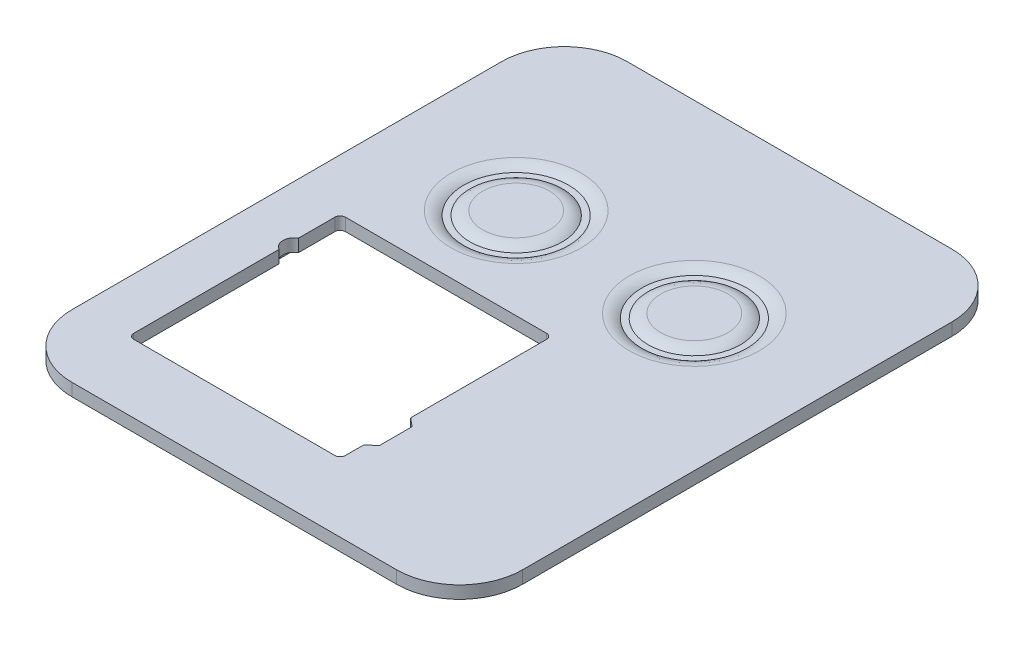
SolidWorks part; units mm, degrees
ref_plane "Front Plane" through (0, 0, 0) normal (0, 0, 1) x (1, 0, 0)
ref_plane "Top Plane" through (0, 0, 0) normal (0, 1, 0) x (1, 0, 0)
ref_plane "Right Plane" through (0, 0, 0) normal (1, 0, 0) x (0, 0, -1)
sketch "Sketch1" plane through (0, 0, 0) normal (0, 1, 0) x (1, 0, 0)
  line L1 (-7.75, -13.25) -> (7.75, -13.25)
  line L2 (-10.75, -10.25) -> (-10.75, 10.25)
  line L3 (-7.75, 13.25) -> (7.75, 13.25)
  line L4 (10.75, -10.25) -> (10.75, 10.25)
  line L5 (-10.75, -13.25) -> (10.75, 13.25) construction
  line L6 (-10.75, 13.25) -> (10.75, -13.25) construction
  arc A0 (-7.75, -13.25) -> (-10.75, -10.25) centre (-7.75, -10.25) cw
  arc A1 (7.75, -13.25) -> (10.75, -10.25) centre (7.75, -10.25) ccw
  arc A2 (7.75, 13.25) -> (10.75, 10.25) centre (7.75, 10.25) cw
  arc A3 (-10.75, 10.25) -> (-7.75, 13.25) centre (-7.75, 10.25) cw
  point P0 (0, 0)
  dimension "D3" = 3
  dimension "D1" = 21.5
  dimension "D2" = 26.5
extrude "Boss-Extrude1" add sketch "Sketch1" along normal blind 0.6
sketch "Sketch2" plane through (0, 0.6, 0) normal (0, 1, 0) x (1, 0, 0)
  line L1 (1.55, -0.15) -> (-8.05, -0.15) construction
  line L2 (1.55, -0.15) -> (1.55, -9.75) construction
  line L3 (1.55, -9.75) -> (-8.05, -9.75) construction
  line L4 (-8.05, -0.15) -> (-8.05, -9.75) construction
  line L6 (-10.75, 10.25) -> (-10.75, -10.25) construction
  line L7 (-7.75, -13.25) -> (7.75, -13.25) construction
  line L9 (1.55, -10) -> (-8.05, -10)
  line L10 (1.8, -9.75) -> (1.8, -0.15)
  line L11 (1.55, 0.1) -> (-8.05, 0.1)
  line L12 (-8.3, -9.75) -> (-8.3, -0.15)
  arc A0 (-8.05, -10) -> (-8.3, -9.75) centre (-8.05, -9.75) cw
  arc A1 (1.55, -10) -> (1.8, -9.75) centre (1.55, -9.75) ccw
  arc A2 (1.8, -0.15) -> (1.55, 0.1) centre (1.55, -0.15) ccw
  arc A3 (-8.05, 0.1) -> (-8.3, -0.15) centre (-8.05, -0.15) ccw
  dimension "D9" = 0.25
  dimension "D1" = 2.7
  dimension "D2" = 3.5
  dimension "D3" = 9.6
  dimension "D4" = 9.6
  dimension "D5" = 0.25
  dimension "D6" = 0.25
  dimension "D7" = 0.25
  dimension "D8" = 0.25
extrude "Cut-Extrude1" cut sketch "Sketch2" against normal blind 2
sketch "Sketch3" plane through (0, 0.6, 0) normal (0, 1, 0) x (1, 0, 0)
  line L2 (2.2, -6.9693) -> (2.2, -8.5311)
  line L3 (2.2, -8.5311) -> (1.8, -8.8672)
  line L5 (2.2, -6.9693) -> (1.8, -6.6332)
  line L6 (1.8, -9.75) -> (1.8, -0.15) construction
  line L7 (-10.75, 10.25) -> (-10.75, -10.25) construction
  line L9 (-7.75, -13.25) -> (7.75, -13.25) construction
  line L11 (1.8, -8.8672) -> (1.8, -6.6332)
  line L12 (-8.05, -10) -> (1.55, -10) construction
  circle A0 centre (-8.05, -2.35) radius 0.525
  dimension "D1" = 1.05
  dimension "D2" = 2.7
  dimension "D3" = 10.9
  dimension "D4" = 0.4
  dimension "D5" = 1.1328
  dimension "D6" = 3.3668
  dimension "D7" = 0.336
  dimension "D8" = 0.3361
extrude "Cut-Extrude2" cut sketch "Sketch3" against normal blind 10
sketch "Sketch4" plane through (0, 0, 0) normal (0, -1, 0) x (-1, 0, 0)
  line L0 (7.75, -13.25) -> (-7.75, -13.25) construction
  line L1 (7.75, 12.25) -> (-7.75, 12.25)
  line L2 (9.75, 10.25) -> (9.75, -10.25)
  line L3 (7.75, -12.25) -> (-7.75, -12.25)
  line L4 (-9.75, 10.25) -> (-9.75, -10.25)
  line L5 (9.75, 12.25) -> (-9.75, -12.25) construction
  line L6 (9.75, -12.25) -> (-9.75, 12.25) construction
  line L7 (-10.75, -10.25) -> (-10.75, 10.25) construction
  line L9 (7.75, 11.5) -> (-7.75, 11.5)
  line L10 (9, 10.25) -> (9, -10.25)
  line L11 (7.75, -11.5) -> (-7.75, -11.5)
  line L12 (-9, 10.25) -> (-9, -10.25)
  line L13 (9, 11.5) -> (-9, -11.5) construction
  line L14 (9, -11.5) -> (-9, 11.5) construction
  arc A1 (7.75, 12.25) -> (9.75, 10.25) centre (7.75, 10.25) cw
  arc A2 (-7.75, 12.25) -> (-9.75, 10.25) centre (-7.75, 10.25) ccw
  arc A3 (-7.75, -12.25) -> (-9.75, -10.25) centre (-7.75, -10.25) cw
  arc A4 (9.75, -10.25) -> (7.75, -12.25) centre (7.75, -10.25) cw
  arc A5 (7.75, 11.5) -> (9, 10.25) centre (7.75, 10.25) cw
  arc A6 (-7.75, 11.5) -> (-9, 10.25) centre (-7.75, 10.25) ccw
  arc A7 (-7.75, -11.5) -> (-9, -10.25) centre (-7.75, -10.25) cw
  arc A8 (9, -10.25) -> (7.75, -11.5) centre (7.75, -10.25) cw
  point P0 (0, 0)
  point P23 (0, 0)
  dimension "D3" = 2
  dimension "D6" = 1.25
  dimension "D1" = 1
  dimension "D2" = 1
  dimension "D4" = 0.75
  dimension "D5" = 0.75
extrude "Boss-Extrude2" add sketch "Sketch4" along normal blind 0.5
sketch "Sketch5" plane through (0, 0, 0) normal (0, -1, 0) x (-1, 0, 0)
  line L0 (-7.75, 13.25) -> (7.75, 13.25) construction
  line L1 (10.75, 10.25) -> (10.75, -10.25) construction
  line L2 (-10.75, -10.25) -> (-10.75, 10.25) construction
  circle A0 centre (-4.25, 4.45) radius 2.5
  circle A1 centre (4.25, 4.45) radius 2.5
  dimension "D1" = 8.8
  dimension "D5" = 5
  dimension "D2" = 8.8
  dimension "D3" = 6.5
  dimension "D4" = 6.5
extrude "Boss-Extrude3" add sketch "Sketch5" along normal blind 1.3
sketch "Sketch6" plane through (0, 0.6, 0) normal (0, 1, 0) x (1, 0, 0)
  circle A0 centre (4.25, 4.45) radius 2.5
  circle A1 centre (-4.25, 4.45) radius 2.5
  circle A2 centre (4.25, 4.45) radius 2.5 construction
  circle A3 centre (-4.25, 4.45) radius 2.5 construction
  circle A4 centre (-4.25, 4.45) radius 2.2
  circle A5 centre (4.25, 4.45) radius 2.2
  dimension "D1" = 5
  dimension "D2" = 4.4
extrude "Cut-Extrude3" cut sketch "Sketch6" against normal blind 0.2
fillet "Fillet1" radius 1 4 edges at (4.25, 0.6, -1.95) (4.25, 0.6, -2.25) (-4.25, 0.6, -2.25) (-4.25, 0.6, -1.95)
chamfer "Chamfer1" distance 1 angle 45 2 edges at (-4.25, -1.3, -6.95) (4.25, -1.3, -6.95)
